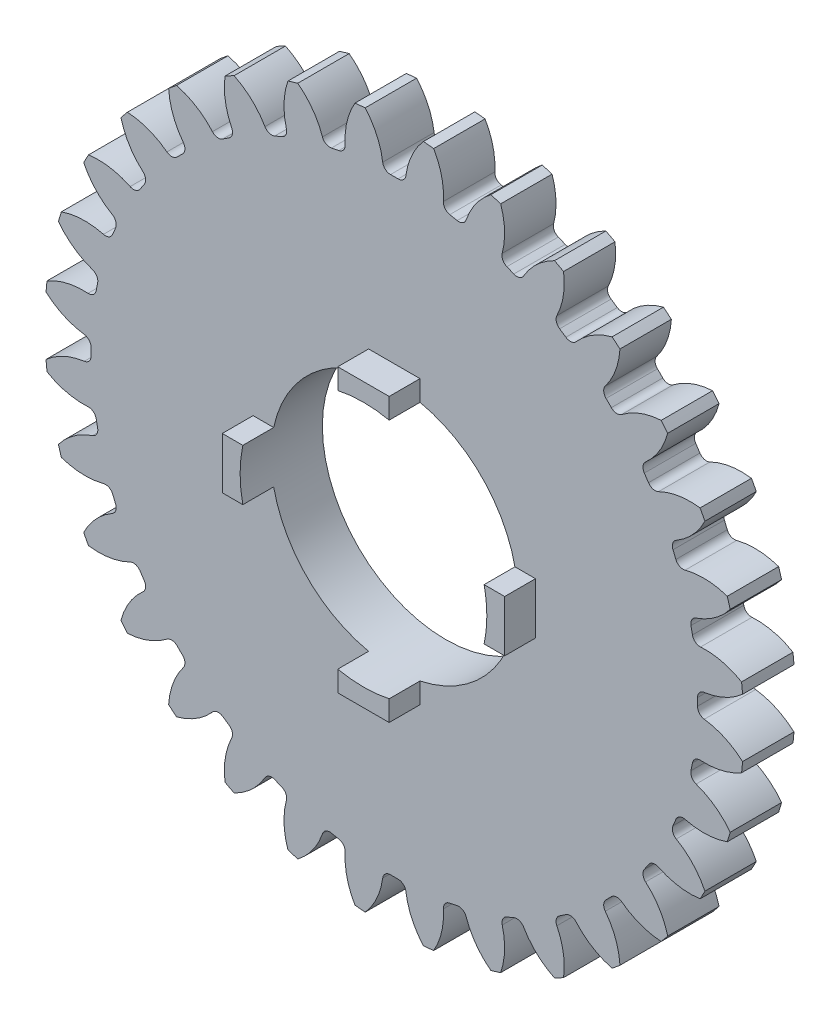
SolidWorks part; units mm, degrees
ref_plane "Front Plane" through (0, 0, 0) normal (0, 0, 1) x (1, 0, 0)
ref_plane "Top Plane" through (0, 0, 0) normal (0, 1, 0) x (1, 0, 0)
ref_plane "Right Plane" through (0, 0, 0) normal (1, 0, 0) x (0, 0, -1)
sketch "Sketch1" plane through (0, 0, 0) normal (0, 0, 1) x (1, 0, 0)
  line L4 (-1.071, 29.4806) -> (0, 0) construction
  line L5 (0, 0) -> (0, 34) construction
  line L6 (0, 0) -> (3.3326, 33.8363) construction
  line L7 (-1.6208, 31.9589) -> (0.7824, 32.9742) construction
  line L8 (-1.6208, 31.9589) -> (0.4018, 32.0615) construction
  line L11 (1.6208, 31.9589) -> (-1.6208, 31.9589) construction
  circle A0 centre (0, 0) radius 29.5
  circle A1 centre (0, 0) radius 32 construction
  circle A2 centre (0, 0) radius 34
  arc A3 (-2.8346, 33.8816) -> (-1.071, 29.4806) centre (-8.0794, 29.2259) cw
  arc A4 (2.8346, 33.8816) -> (1.071, 29.4806) centre (8.0794, 29.2259) ccw
  point P5 (-32, 0)
  point P6 (-34, 0)
  point P7 (-29.5, 0)
  point P12 (-1.6208, 31.9589)
  point P22 (1.6208, 31.9589)
  dimension "D5" = 64
  dimension "D1" = 2.5
  dimension "D2" = 2
  dimension "D3" = 20
  dimension "D4" = 3.2416
  dimension "D6" = 5.625
  dimension "D7" = 0.5
extrude "Boss-Extrude1" add sketch "Sketch1" against normal blind 5 contours A2
extrude "Cut-Extrude1" cut sketch "Sketch1<4>" against normal blind 10 contours A4 A2 A3 A0 region at (0, 32.1215, 0)
sketch "Sketch1<4>" plane through (0, 0, 0) normal (0, 0, 1) x (1, 0, 0) same geometry as "Sketch1"
fillet "Fillet2" radius 0.76 2 edges at (1.071, 29.4806, -2.5) (-1.071, 29.4806, -2.5)
ref_axis "Axis1" through (0, 0, 0) along (0, 0, 1)
pattern_circular "CirPattern2" count 32 over 360 about axis through (0, 0, 0) along (0, 0, 1) of "Cut-Extrude1", "Fillet2"
sketch "Sketch2" plane through (0, 0, 0) normal (0, 0, 1) x (1, 0, 0)
  circle A0 centre (0, 0) radius 12
  dimension "D1" = 24
extrude "Cut-Extrude2" cut sketch "Sketch2" against normal up to surface (5 mm away) up to face at (0, 0, -5)
sketch "Sketch3" plane through (0, 0, 0) normal (0, 0, 1) x (1, 0, 0)
  line L0 (-2.5, 11.7367) -> (-2.5, 13.7367)
  line L1 (-2.5, 13.7367) -> (2.5, 13.7367)
  line L2 (2.5, 13.7367) -> (2.5, 11.7367)
  line L3 (0, 0) -> (0, 12) construction
  line L4 (13.7367, -2.5) -> (11.7367, -2.5)
  line L5 (13.7367, 2.5) -> (13.7367, -2.5)
  line L6 (11.7367, 2.5) -> (13.7367, 2.5)
  line L7 (-2.5, -13.7367) -> (-2.5, -11.7367)
  line L8 (2.5, -13.7367) -> (-2.5, -13.7367)
  line L9 (2.5, -11.7367) -> (2.5, -13.7367)
  line L10 (-13.7367, 2.5) -> (-11.7367, 2.5)
  line L11 (-13.7367, -2.5) -> (-13.7367, 2.5)
  line L12 (-11.7367, -2.5) -> (-13.7367, -2.5)
  circle A0 centre (0, 0) radius 12 construction
  arc A1 (-2.5, 11.7367) -> (2.5, 11.7367) centre (0, 0) cw
  arc A2 (11.7367, 2.5) -> (11.7367, -2.5) centre (0, 0) cw
  arc A3 (2.5, -11.7367) -> (-2.5, -11.7367) centre (0, 0) cw
  arc A4 (-11.7367, -2.5) -> (-11.7367, 2.5) centre (0, 0) cw
  point P24 (0, 0)
  dimension "D4" = 4
  dimension "D1" = 2.5
  dimension "D2" = 2.5
  dimension "D3" = 2
extrude "Boss-Extrude2" add sketch "Sketch3" along normal blind 3
equation "\"backlash\"= 0.1mm"
equation "\"module\"= 2mm"
equation "\"pressureAngle\"= 20deg"
equation "\"width\"= 10mm"
equation "\"D1@Sketch1\"= 1.25 * \"module\""
equation "\"D2@Sketch1\"=\"module\""
equation "\"D5@Sketch1\"=\"module\"*\"numberOfTeeth\""
equation "\"D1@Boss-Extrude1\"=\"width\"-5"
equation "\"D3@Sketch1\"=\"pressureAngle\""
equation "\"D1@Cut-Extrude1\"=\"width\""
equation "\"D1@CirPattern2\"=\"numberOfTeeth\""
equation "\"D1@Fillet2\"=0.38*\"module\""
equation "\"D4@Sketch1\"=pi*\"module\"/2+\"backlash\""
equation "\"numberOfTeeth\"= 32"
equation "\"D6@Sketch1\"=180/\"numberOfTeeth\""
equation "\"toothTipProfile\"= 1mm"
equation "\"D7@Sketch1\"=\"toothTipProfile\"/2"
equation "\"lengthOverallRack\"= pi * \"module\" * \"numberOfTeethRack\""
equation "\"numberOfTeethRack\"= 20"
